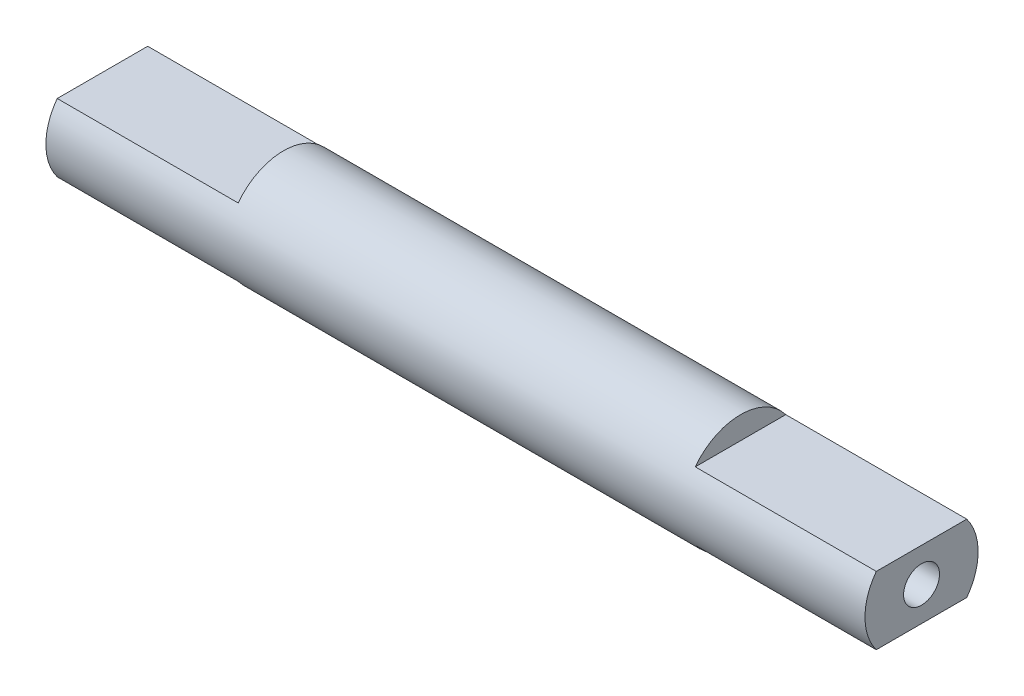
SolidWorks part; units mm, degrees
ref_plane "Alzado" through (0, 0, 0) normal (0, 0, 1) x (1, 0, 0)
ref_plane "Planta" through (0, 0, 0) normal (0, 1, 0) x (1, 0, 0)
ref_plane "Vista lateral" through (0, 0, 0) normal (1, 0, 0) x (0, 0, -1)
sketch "Croquis1" plane through (0, 0, 0) normal (1, 0, 0) x (0, 0, -1)
  circle A0 centre (0, 0) radius 2.5
extrude "Saliente-Extruir1" add sketch "Croquis1" along normal blind 36.2
sketch "Croquis2" plane through (36.2, 0, 0) normal (1, 0, 0) x (0, 0, -1)
  line L1 (-2.5933, -1.5) -> (2.5933, -1.5)
  line L2 (-2.5933, -1.5) -> (-2.5933, 1.5)
  line L3 (-2.5933, 1.5) -> (2.5933, 1.5)
  line L4 (2.5933, -1.5) -> (2.5933, 1.5)
  line L5 (-2.5933, -1.5) -> (2.5933, 1.5) construction
  line L6 (-2.5933, 1.5) -> (2.5933, -1.5) construction
  circle A0 centre (0, 0) radius 0.7937
  point P0 (0, 0)
  dimension "D1" = 3
extrude "Cortar-Extruir1" cut sketch "Croquis2" against normal blind 8 flip side to cut contours L3 L4 L1 L2
extrude "Cortar-Extruir2" cut sketch "Croquis2<3>" against normal blind 5 contours A0 region at (36.2, 0, 0)
sketch "Croquis2<3>" plane through (36.2, 0, 0) normal (1, 0, 0) x (0, 0, -1) same geometry as "Croquis2"
sketch "Croquis3" plane through (0, 0, 0) normal (1, 0, 0) x (0, 0, -1)
  line L2 (2, 1.5) -> (-2, 1.5)
  line L3 (-2, -1.5) -> (2, -1.5)
  line L4 (2, 1.5) -> (-2, 1.5)
  line L5 (-2, -1.5) -> (2, -1.5)
  arc A2 (-2, 1.5) -> (-2, -1.5) centre (0, 0) ccw
  arc A3 (2, -1.5) -> (2, 1.5) centre (0, 0) ccw
  arc A4 (-2, 1.5) -> (-2, -1.5) centre (0, 0) ccw
  arc A5 (2, -1.5) -> (2, 1.5) centre (0, 0) ccw
  dimension "D1" = 0
extrude "Cortar-Extruir3" cut sketch "Croquis3" along normal blind 8 flip side to cut
sketch "Croquis4" plane through (0, 0, 0) normal (-1, 0, 0) x (0, 0, 1)
  circle A0 centre (0, 0) radius 0.7937
extrude "Cortar-Extruir4" cut sketch "Croquis4" against normal blind 5
